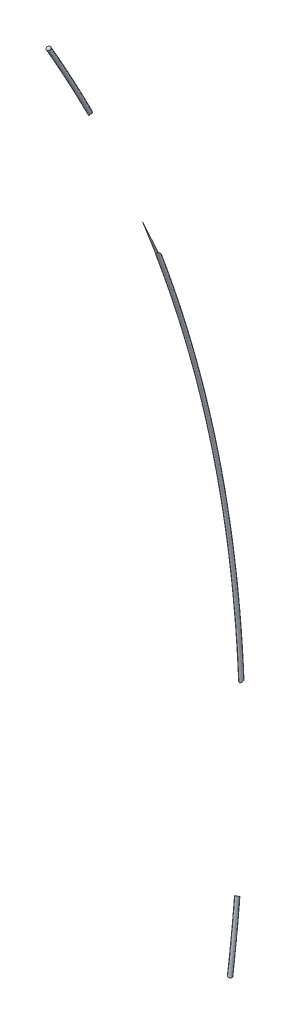
SolidWorks part; units mm, degrees
ref_plane "Front Plane" through (0, 0, 0) normal (1, 0, 0) x (0, 1, 0)
ref_plane "Top Plane" through (0, 0, 0) normal (0, 0, 1) x (0, 1, 0)
ref_plane "Right Plane" through (0, 0, 0) normal (0, 1, 0) x (-1, 0, 0)
sketch "Sketch1" plane through (0, 0, 0) normal (1, 0, 0) x (0, 1, 0)
  spline S0 degree 2 poles (0, 0) (38.7728, -5.0789) (73.2967, 14.8675) knots 0 0 0 1 1 1
  dimension "D1" = 76.2
sweep "Sweep1" add path "Sketch1" circular profile diameter 0.3175 parameters "D3"=0.3175
